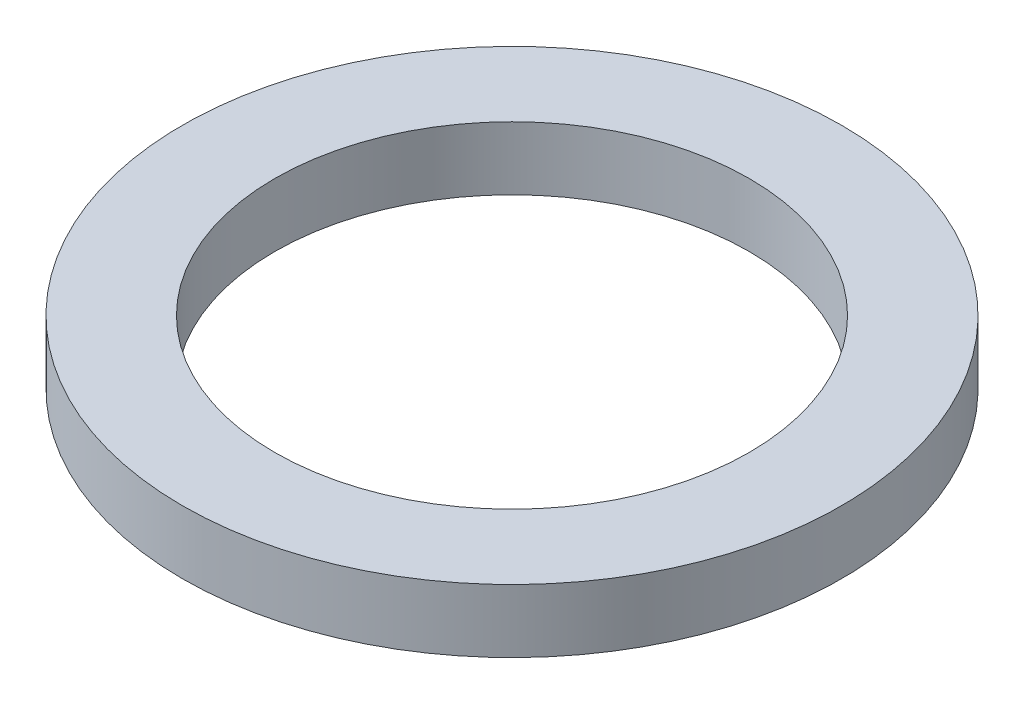
SolidWorks part; units mm, degrees
ref_plane "Front Plane" through (0, 0, 0) normal (0, 0, 1) x (1, 0, 0)
ref_plane "Top Plane" through (0, 0, 0) normal (0, 1, 0) x (1, 0, 0)
ref_plane "Right Plane" through (0, 0, 0) normal (1, 0, 0) x (0, 0, -1)
sketch "Sketch1" plane through (0, 0, 0) normal (0, 1, 0) x (1, 0, 0)
  circle A0 centre (0, 0) radius 62.5
  dimension "FLANGE_OD" = 125
extrude "Boss-Extrude1" add sketch "Sketch1" along normal blind 12
sketch "Sketch2" plane through (0, 0, 0) normal (0, 1, 0) x (1, 0, 0)
  circle A0 centre (0, 0) radius 45
  dimension "BORE_D" = 90
extrude "Cut-Extrude1" cut sketch "Sketch2" along normal through all
sketch "Sketch3" plane through (0, 12, 0) normal (0, 1, 0) x (1, 0, 0)
  circle A0 centre (0, 0) radius 26.4813 construction
  circle A1 centre (-26.4813, 0) radius 3.1278
  dimension "BOLT_D" = 6.2557
  dimension "BOLT_PCD" = 52.9626
extrude "Cut-Extrude2" cut sketch "Sketch3" against normal blind 7.27 rebuild error yes
pattern_circular "CirPattern1" count 4 over 360 rebuild error yes
